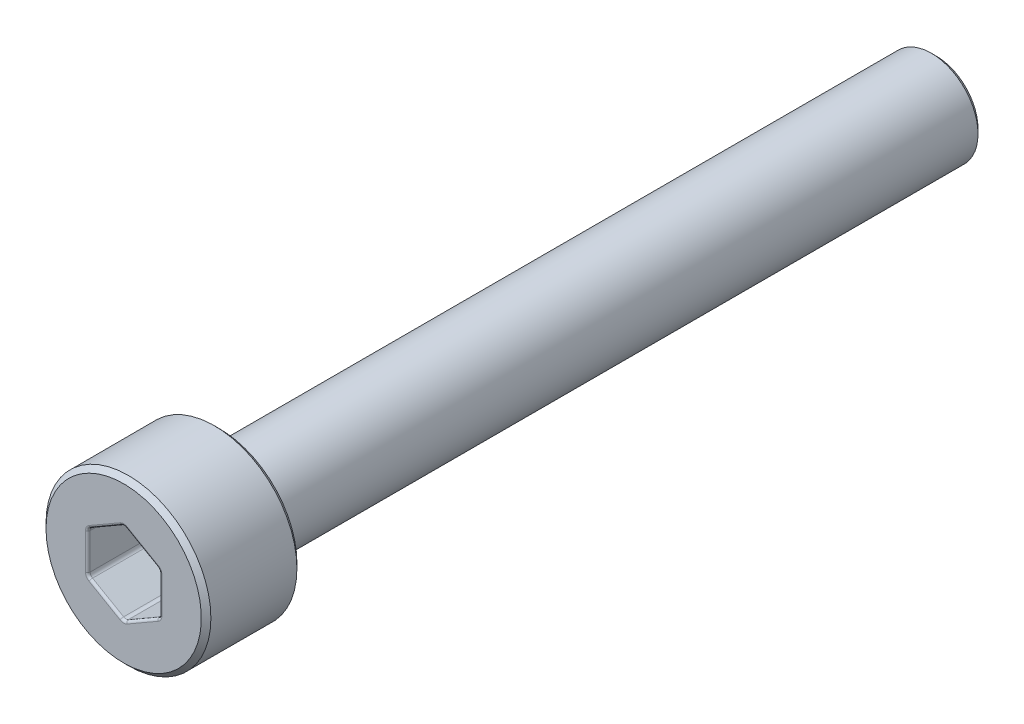
SolidWorks part; units mm, degrees
material "1.4000 (X6Cr13)"
ref_plane "Ebene vorne" through (0, 0, 0) normal (0, 0, 1) x (1, 0, 0)
ref_plane "Ebene oben" through (0, 0, 0) normal (0, 1, 0) x (1, 0, 0)
ref_plane "Ebene rechts" through (0, 0, 0) normal (1, 0, 0) x (0, 0, -1)
sketch "Skizze1" plane through (0, 0, 0) normal (1, 0, 0) x (0, 0, -1)
  line L0 (-21.9199, 0) -> (33.7608, 0) construction
  line L1 (0, 13.9907) -> (0, -9.4798) construction
  line L2 (-4, 0) -> (-4, 3.45)
  line L3 (-4, 3.45) -> (0, 3.45)
  line L4 (0, 3.45) -> (0, 1.95)
  line L5 (0, 1.95) -> (30, 1.95)
  line L6 (30, 1.95) -> (30, 0)
  line L7 (30, 0) -> (-4, 0)
  dimension "D1" = 3.9
  dimension "D2" = 4
  dimension "D3" = 6.9
  dimension "D4" = 30
revolve "Rotation1" add sketch "Skizze1" angle 360 about L0
sketch "Skizze2" plane through (0, 0, 4) normal (0, 0, 1) x (1, 0, 0)
  line L0 (0, 8.6995) -> (0, -7.3778) construction
  line L1 (1.5, -0.866) -> (1.5, 0.866)
  line L2 (1.5, 0.866) -> (0, 1.7321)
  line L3 (0, 1.7321) -> (-1.5, 0.866)
  line L4 (-1.5, 0.866) -> (-1.5, -0.866)
  line L5 (-1.5, -0.866) -> (0, -1.7321)
  line L6 (0, -1.7321) -> (1.5, -0.866)
  circle A0 centre (0, 0) radius 1.5 construction
  dimension "D1" = 3
extrude "Schnitt-Linear austragen1" cut sketch "Skizze2" against normal blind 2.5
chamfer "Fase1" distance 0.2 angle 45 3 edges at (3.45, 0, 4) (3.45, 0, 0) (1.95, 0, -30)
fillet "Verrundung1" radius 0.2 13 edges at (-0.75, -1.299, 1.5) (-1.5, 0, 1.5) (-0.75, 1.299, 1.5) (0.75, 1.299, 1.5) (1.5, 0, 1.5) (0.75, -1.299, 1.5) (-1.5, -0.866, 2.75) (0, -1.7321, 2.75) (1.5, -0.866, 2.75) (1.5, 0.866, 2.75) (0, 1.7321, 2.75) (-1.5, 0.866, 2.75) (1.95, 0, 0)
fillet "Verrundung2" radius 0.1 12 edges at (1.4732, -0.8506, 4) (0.75, -1.299, 4) (0, -1.7011, 4) (-0.75, -1.299, 4) (-1.4732, -0.8506, 4) (-1.5, 0, 4) (-1.4732, 0.8506, 4) (-0.75, 1.299, 4) (0, 1.7011, 4) (0.75, 1.299, 4) (1.4732, 0.8506, 4) (1.5, 0, 4)
ref_axis "Achse1" through (0, 0, -19.6323) along (0, 0, 1)
